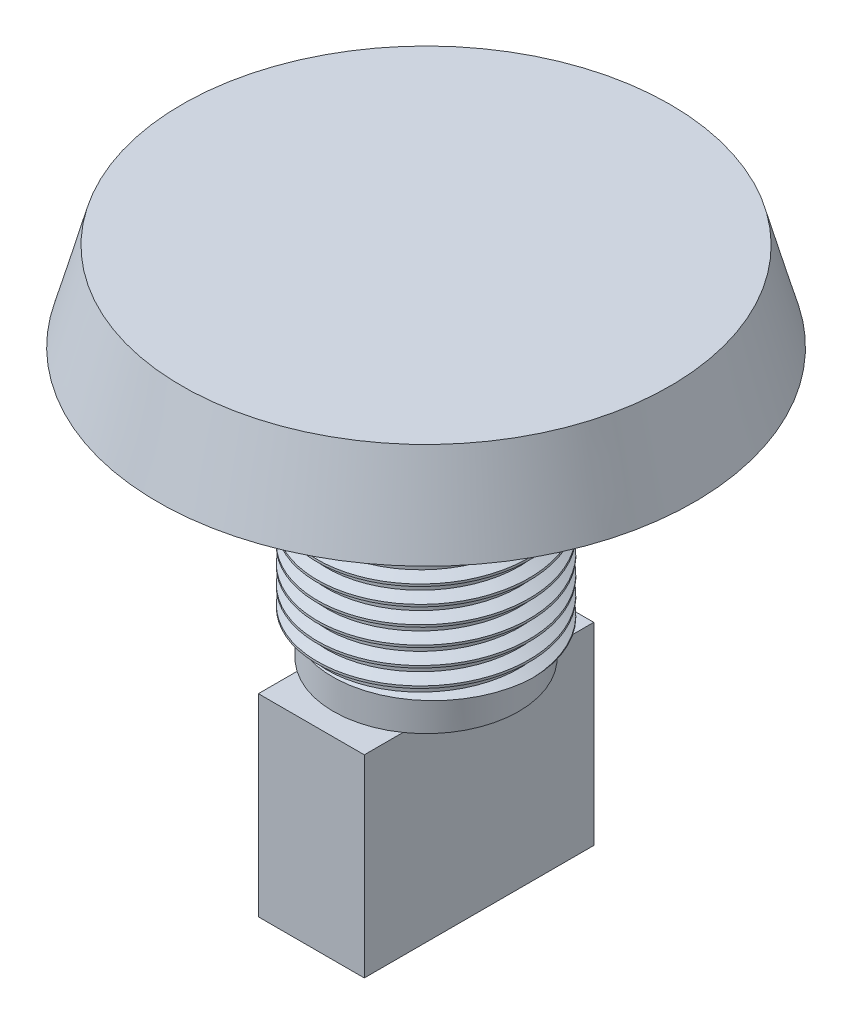
SolidWorks part; units mm, degrees
note: '?' marks a value the reader was unsure of.
material "ABS"
ref_plane "Front Plane" through (0, 0, 0) normal (0, 0, 1) x (1, 0, 0)
ref_plane "Top Plane" through (0, 0, 0) normal (0, 1, 0) x (1, 0, 0)
ref_plane "Right Plane" through (0, 0, 0) normal (1, 0, 0) x (0, 0, -1)
sketch "Sketch1" plane through (0, 0, 0) normal (0, 0, 1) x (1, 0, 0)
  line L0 (0, 0) -> (0, 10)
  line L1 (0, 0) -> (-30.4, 0)
  line L2 (-30.4, 0) -> (-27.65, 10)
  line L3 (-27.65, 10) -> (0, 10)
  dimension "D1" = 30.4
  dimension "D2" = 10
  dimension "D3" = 27.65
revolve "Revolve1" add sketch "Sketch1" angle 360 about L0
sketch "Sketch2" plane through (0, 0, 0) normal (0, -1, 0) x (1, 0, 0)
  circle A0 centre (0, 0) radius 12
  dimension "D1" = 24
extrude "Boss-Extrude1" add sketch "Sketch2" along normal blind 30.5
thread "Thread1" pitch 2 start angle 0, offset 0, length 0, pitch 2, diameter 24
ref_plane "Plane1" through (12, -30.5, 0) normal (0, 0, 1) x (1, 0, 0)
sketch "Thread Profile1" plane through (12, -30.5, 0) normal (0, 0, 1) x (1, 0, 0)
  line L0 (0, 0) -> (0, 2) construction
  line L11 (0, 0) -> (0, 1.75)
  line L12 (0, 1.75) -> (-1.0825, 1.125)
  line L13 (-1.0825, 1.125) -> (-1.0825, 0.625)
  line L15 (-1.0825, 0.625) -> (0, 0)
  line L17 (-1.0825, 0.875) -> (0, 0.875) construction
  point P2 (0, 0)
  dimension "Pitch" = 2
  dimension "Profile_Angle" = 60
  dimension "Profile_Land" = 0.5
  dimension "Profile_Height" = 1.0825
sketch "Sketch8" plane through (0, -30.5, 0) normal (0, -1, 0) x (1, 0, 0)
  circle A0 centre (0, 0) radius 12
  circle A1 centre (0, 0) radius 10.5
  dimension "D1" = 21
extrude "Cut-Extrude1" cut sketch "Sketch8" against normal blind 4
sketch "Sketch9" plane through (0, -30.5, 0) normal (0, -1, 0) x (1, 0, 0)
  line L0 (6, 0) -> (-6, 0) construction
  line L1 (6, 13) -> (-6, 13)
  line L2 (6, 13) -> (6, -13)
  line L3 (6, -13) -> (-6, -13)
  line L4 (-6, 13) -> (-6, -13)
  line L5 (0, 13) -> (0, 0) construction
  dimension "D1" = 12
  dimension "D2" = 26
extrude "Boss-Extrude2" add sketch "Sketch9" along normal blind 21.9
sketch "Sketch10" plane through (0, 0, 0) normal (0, -1, 0) x (1, 0, 0)
  line L0 (0, 18.85) -> (0, -18.85) construction
  circle A0 centre (0, -18.85) radius 1.65
  circle A1 centre (0, 18.85) radius 1.65
  point P6 (0, 0)
  dimension "D1" = 3.3
  dimension "D2" = 37.7
extrude "Boss-Extrude3" add sketch "Sketch10" along normal blind 4
ref_axis "Axis1" through (0, 0, 0) along (0, 1, 0)?
